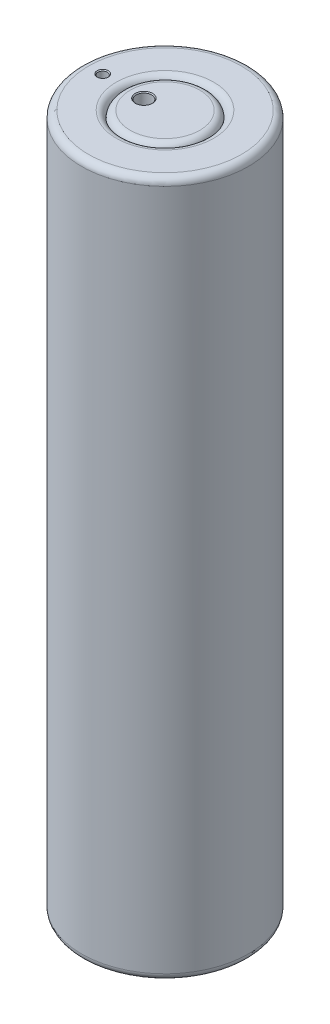
SolidWorks part; units mm, degrees
ref_plane "Plan de face" through (0, 0, 0) normal (0, 0, 1) x (1, 0, 0)
ref_plane "Plan de dessus" through (0, 0, 0) normal (0, 1, 0) x (1, 0, 0)
ref_plane "Plan de droite" through (0, 0, 0) normal (1, 0, 0) x (0, 0, -1)
sketch "Esquisse2" plane through (0, 0, 0) normal (1, 0, 0) x (0, 0, -1)
  line L0 (12.834, -467.6677) -> (12.834, -477.6677)
  line L1 (-17.166, 22.3323) -> (12.834, 22.3323)
  line L2 (-17.166, 22.3323) -> (-17.166, -477.6677)
  line L3 (-17.166, -477.6677) -> (12.834, -477.6677)
  line L4 (12.834, 22.3323) -> (12.834, 12.3323)
  line L5 (12.834, 12.3323) -> (-13.166, 12.3323)
  line L7 (12.834, -467.6677) -> (-13.166, -467.6677)
  line L8 (-13.166, 12.3323) -> (-13.166, -467.6677)
  dimension "D1" = 30
  dimension "D2" = 500
  dimension "D3" = 10
  dimension "D4" = 10
  dimension "D5" = 4
revolve "Révolution1" add sketch "Esquisse2" angle 360 about L0
fillet "Congé1" radius 5 1 edges at (0, 22.3323, 17.166)
fillet "Congé2" radius 5 1 edges at (0, -477.6677, 17.166)
sketch "Esquisse3" plane through (0, 0, 0) normal (1, 0, 0) x (0, 0, -1)
  line L0 (37.834, 22.3323) -> (-12.166, 22.3323) construction
  line L1 (-47.166, 22.3323) -> (-17.166, 22.3323)
  line L2 (-47.166, 22.3323) -> (-47.166, -477.6677)
  line L3 (-47.166, -477.6677) -> (-17.166, -477.6677)
  line L4 (-17.166, 22.3323) -> (-17.166, -477.6677)
  line L5 (-17.166, 17.3323) -> (-17.166, -472.6677) construction
  line L6 (42.834, -472.6677) -> (42.834, 17.3323) construction
  line L8 (-43.166, 12.3323) -> (-21.166, 12.3323)
  line L9 (-43.166, 12.3323) -> (-43.166, -467.6677)
  line L10 (-43.166, -467.6677) -> (-21.166, -467.6677)
  line L11 (-21.166, 12.3323) -> (-21.166, -467.6677)
  dimension "D1" = 500
  dimension "D2" = 0
  dimension "D3" = 0
  dimension "D4" = 90
  dimension "D5" = 10
  dimension "D6" = 4
  dimension "D7" = 4
  dimension "D8" = 10
ref_axis "Axe1" through (0, -472.6677, -12.834) along (0, 1, 0)
revolve "Révolution2" add sketch "Esquisse3" angle 360 about axis through (0, -472.6677, -12.834) along (0, 1, 0)
fillet "Congé3" radius 5 2 edges at (0, 22.3323, -72.834) (0, 22.3323, -42.834)
fillet "Congé4" radius 5 2 edges at (0, -477.6677, -42.834) (0, -477.6677, -72.834)
sketch "Esquisse4" plane through (0, 22.3323, 0) normal (0, 1, 0) x (1, 0, 0)
  point P0 (-14.999, 12.6567)
  point P1 (14.9991, 12.6666)
  dimension "D1" = 15
  dimension "D2" = 15
hole_wizard "Perçage pour tuyau pour trou taraudé 1/41" positions "Esquisse3D1" profile "Esquisse5" hole size "1/4" standard "Ansi Inch" end condition up to next
sketch3d "Esquisse3D1"
  point P0 (-14.999, 22.3323, -12.6567)
sketch "Esquisse5" plane through (-14.999, 22.3323, -12.6567) normal (1, 0, 0) x (0, 0, 1)
  line L0 (0, 0) -> (0, 10)
  line L1 (0, 10) -> (5.5626, 10)
  line L2 (5.5626, 10) -> (5.5626, 0.635)
  line L3 (5.5626, 0.635) -> (6.1976, 0)
  line L5 (6.1976, 0) -> (0, 0)
  line L6 (-5.5626, 0.635) -> (-6.1976, 0) construction
  line L11 (0, -6.35) -> (0, 107.95) construction
  dimension "Diamètre du perçage jusqu'au prochain" = 11.1252
  dimension "Profondeur du perçage jusqu'au prochain" = 10
  dimension "Diamètre du fraisage entrant" = 12.3952
  dimension "Angle du fraisage entrant" = 90
sketch "Esquisse8" plane through (0, -477.6677, 0) normal (0, -1, 0) x (1, 0, 0)
  point P0 (-44.9995, -13.042)
  point P1 (-14.9985, -13.0495)
  dimension "D1" = 45
  dimension "D2" = 15
hole_wizard "Dégagement 1/21" positions "Esquisse3D4" profile "Esquisse10" hole size "1/2" standard "Ansi Inch" end condition up to next
sketch3d "Esquisse3D4"
  point P0 (-44.9995, -477.6677, -13.042)
sketch "Esquisse10" plane through (-44.9995, -477.6677, -13.042) normal (1, 0, 0) x (0, 0, -1)
  line L0 (0, 0) -> (0, 10)
  line L1 (0, 10) -> (6.7462, 10)
  line L2 (6.7462, 10) -> (6.7462, 0.635)
  line L3 (6.7462, 0.635) -> (7.3812, 0)
  line L5 (7.3812, 0) -> (0, 0)
  line L6 (-6.7462, 0.635) -> (-7.3812, 0) construction
  line L11 (0, -6.35) -> (0, 107.95) construction
  dimension "Diamètre du perçage jusqu'au prochain" = 13.4925
  dimension "Profondeur du perçage jusqu'au prochain" = 10
  dimension "Diamètre du fraisage entrant" = 14.7625
  dimension "Angle du fraisage entrant" = 90
hole_wizard "Perçage pour tuyau pour trou taraudé 1/42" positions "Esquisse13" profile "Esquisse14" hole size "1/4" standard "Ansi Inch" end condition up to next
sketch "Esquisse13" plane through (0, -477.6677, 0) normal (0, -1, 0) x (-1, 0, 0)
  point P0 (14.9985, 13.0495)
sketch "Esquisse14" plane through (-14.9985, -477.6677, -13.0495) normal (1, 0, 0) x (0, 0, -1)
  line L0 (0, 0) -> (0, 10)
  line L1 (0, 10) -> (5.5626, 10)
  line L2 (5.5626, 10) -> (5.5626, 0.635)
  line L3 (5.5626, 0.635) -> (6.1976, 0)
  line L5 (6.1976, 0) -> (0, 0)
  line L6 (-5.5626, 0.635) -> (-6.1976, 0) construction
  line L11 (0, -6.35) -> (0, 107.95) construction
  dimension "Diamètre du perçage jusqu'au prochain" = 11.1252
  dimension "Profondeur du perçage jusqu'au prochain" = 10
  dimension "Diamètre du fraisage entrant" = 12.3952
  dimension "Angle du fraisage entrant" = 90
hole_wizard "Dégagement 1/42" positions "Esquisse15" profile "Esquisse16" hole size "1/4" standard "Ansi Inch" end condition up to next
sketch "Esquisse15" plane through (0, 22.3323, 0) normal (0, 1, 0) x (1, 0, 0)
  point P0 (-44.9995, 13.042)
sketch "Esquisse16" plane through (-44.9995, 22.3323, -13.042) normal (1, 0, 0) x (0, 0, 1)
  line L0 (0, 0) -> (0, 10)
  line L1 (0, 10) -> (3.3782, 10)
  line L2 (3.3782, 10) -> (3.3782, 0.635)
  line L3 (3.3782, 0.635) -> (4.0132, 0)
  line L5 (4.0132, 0) -> (0, 0)
  line L6 (-3.3782, 0.635) -> (-4.0132, 0) construction
  line L11 (0, -6.35) -> (0, 107.95) construction
  dimension "Diamètre du perçage jusqu'au prochain" = 6.7564
  dimension "Profondeur du perçage jusqu'au prochain" = 10
  dimension "Diamètre du fraisage entrant" = 8.0264
  dimension "Angle du fraisage entrant" = 90
sketch "Esquisse17" plane through (0, -477.6677, 0) normal (0, -1, 0) x (1, 0, 0)
  line L0 (0, -12.834) -> (-14.9985, -13.0495) construction
  point P0 (44.9954, -12.1875)
  point P5 (0, 0)
  point P6 (0, 0)
  dimension "D1" = 45
hole_wizard "Dégagement 1/43" positions "Esquisse18" profile "Esquisse19" hole size "1/4" standard "Ansi Inch" end condition up to next
sketch "Esquisse18" plane through (0, -477.6677, 0) normal (0, -1, 0) x (-1, 0, 0)
  point P0 (-44.9954, 12.1875)
sketch "Esquisse19" plane through (44.9954, -477.6677, -12.1875) normal (1, 0, 0) x (0, 0, -1)
  line L0 (0, 0) -> (0, 10)
  line L1 (0, 10) -> (3.3782, 10)
  line L2 (3.3782, 10) -> (3.3782, 0.635)
  line L3 (3.3782, 0.635) -> (4.0132, 0)
  line L5 (4.0132, 0) -> (0, 0)
  line L6 (-3.3782, 0.635) -> (-4.0132, 0) construction
  line L11 (0, -6.35) -> (0, 107.95) construction
  dimension "Diamètre du perçage jusqu'au prochain" = 6.7564
  dimension "Profondeur du perçage jusqu'au prochain" = 10
  dimension "Diamètre du fraisage entrant" = 8.0264
  dimension "Angle du fraisage entrant" = 90
